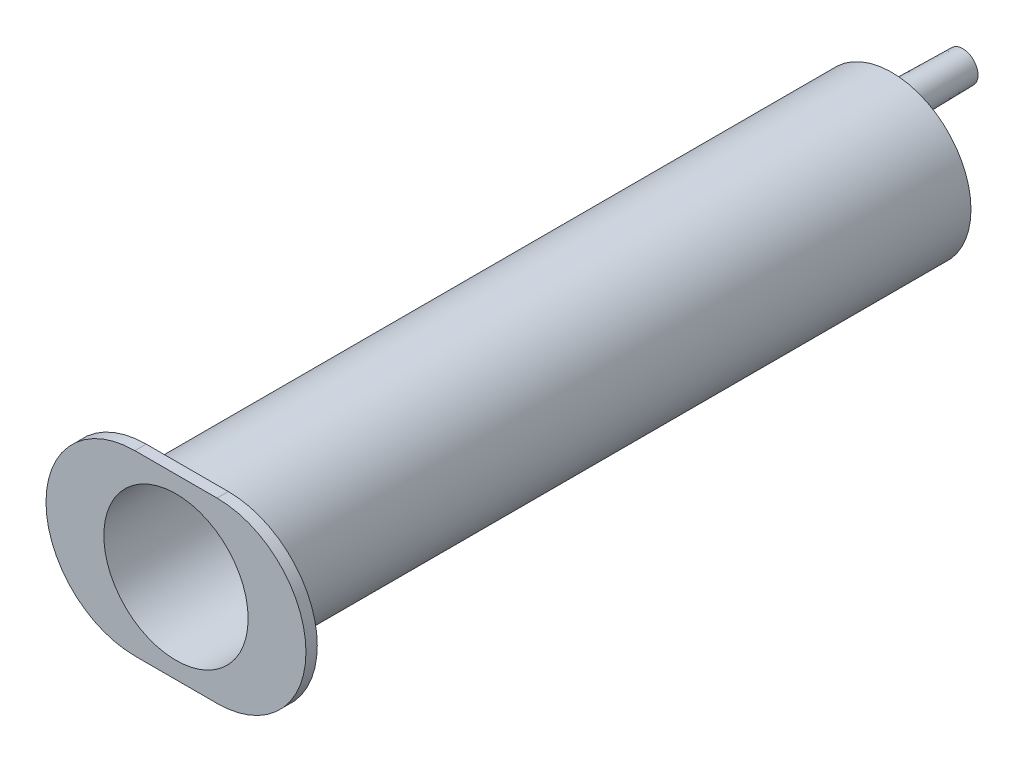
SolidWorks part; units mm, degrees
ref_plane "Front Plane" through (0, 0, 0) normal (0, 0, 1) x (1, 0, 0)
ref_plane "Top Plane" through (0, 0, 0) normal (0, 1, 0) x (1, 0, 0)
ref_plane "Right Plane" through (0, 0, 0) normal (1, 0, 0) x (0, 0, -1)
sketch "Sketch1" plane through (0, 0, 0) normal (0, 0, 1) x (1, 0, 0)
  circle A0 centre (0, 0) radius 10.5
  dimension "D1" = 21
extrude "Boss-Extrude1" add sketch "Sketch1" along normal blind 95
sketch "Sketch2" plane through (0, 0, 95) normal (0, 0, 1) x (1, 0, 0)
  line L0 (5.45, 0) -> (-5.45, 0) construction
  line L1 (5.45, -11.8) -> (-5.45, -11.8)
  line L2 (5.45, 11.8) -> (-5.45, 11.8)
  arc A0 (5.45, -11.8) -> (5.45, 11.8) centre (5.45, 0) ccw
  arc A1 (-5.45, 11.8) -> (-5.45, -11.8) centre (-5.45, 0) ccw
  point P2 (0, 0)
  dimension "D2" = 10.9
  dimension "D1" = 23.6
extrude "Boss-Extrude2" add sketch "Sketch2" against normal blind 1.5
sketch "Sketch3" plane through (0, 0, 0) normal (0, 0, -1) x (-1, 0, 0)
  line L0 (0, -1000) -> (0, 49000) construction
  circle A0 centre (0, 6.5) radius 2.2
  dimension "D1" = 4.4
  dimension "D2" = 6.5
extrude "Boss-Extrude3" add sketch "Sketch3" along normal blind 9.4 draft 1
sketch "Sketch4" plane through (0, 0, 95) normal (0, 0, 1) x (1, 0, 0)
  circle A0 centre (0, 0) radius 9.575
  dimension "D1" = 19.15
extrude "Cut-Extrude1" cut sketch "Sketch4" along direction (0, 0, 1) on the side against the normal offset from surface (93.5 mm away) 1.5 up to face at (10.5, 0, 0)
sketch "Sketch5" plane through (0, 0, -9.4) normal (0, 0, -1) x (-1, 0, 0)
  circle A0 centre (0, 6.5) radius 1
  dimension "D1" = 2
extrude "Cut-Extrude2" cut sketch "Sketch5" against normal through all
